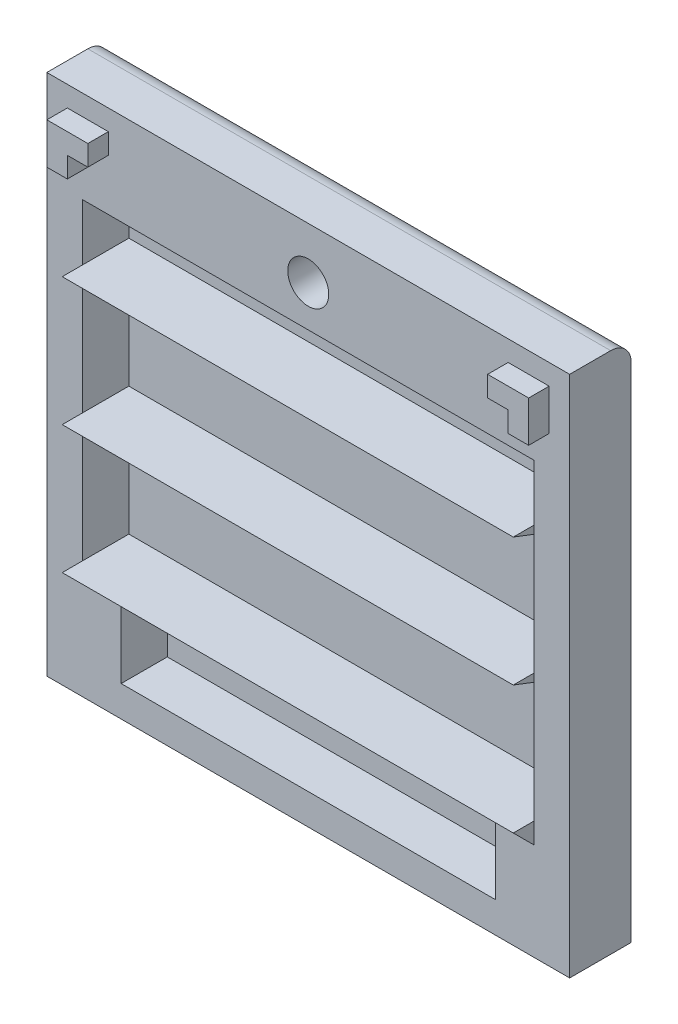
SolidWorks part; units mm, degrees
material "ABS"
ref_plane "Plano frontal" through (0, 0, 0) normal (0, 0, 1) x (1, 0, 0)
ref_plane "Plano superior" through (0, 0, 0) normal (0, 1, 0) x (1, 0, 0)
ref_plane "Plano direito" through (0, 0, 0) normal (1, 0, 0) x (0, 0, -1)
sketch "Esboço1" plane through (0, 0, 0) normal (0, 0, 1) x (1, 0, 0)
  line L1 (25.5, 25.5) -> (-25.5, 25.5)
  line L2 (25.5, 25.5) -> (25.5, -25.5)
  line L3 (25.5, -25.5) -> (-25.5, -25.5)
  line L4 (-25.5, 25.5) -> (-25.5, -25.5)
  line L5 (25.5, 25.5) -> (-25.5, -25.5) construction
  line L6 (25.5, -25.5) -> (-25.5, 25.5) construction
  point P0 (0, 0)
  dimension "D1" = 51
  dimension "D2" = 51
extrude "Ressalto-extrusão1" add sketch "Esboço1" along normal blind 6
sketch "Esboço2" plane through (0, 0, 0) normal (0, 0, -1) x (-1, 0, 0)
  line L0 (25.5, -25.5) -> (-25.5, -25.5) construction
  line L1 (-18.25, -16) -> (18.25, -16)
  line L2 (-18.25, -16) -> (-18.25, -22.5)
  line L3 (-18.25, -22.5) -> (18.25, -22.5)
  line L4 (18.25, -16) -> (18.25, -22.5)
  point P6 (0, -16)
  dimension "D1" = 36.5
  dimension "D2" = 6.5
  dimension "D3" = 3
extrude "Corte-extrusão1" cut sketch "Esboço2" against normal blind 4.5
sketch "Esboço3" plane through (0, 0, 6) normal (0, 0, 1) x (1, 0, 0)
  line L0 (25.5, 25.5) -> (-25.5, 25.5) construction
  circle A1 centre (0, 20.5) radius 2
  dimension "D1" = 4
  dimension "D2" = 5
extrude "Corte-extrusão2" cut sketch "Esboço3" against normal through all
sketch "Esboço4" plane through (0, 0, 0) normal (0, 0, -1) x (-1, 0, 0)
  line L0 (18.25, -16) -> (-18.25, -16) construction
  line L1 (-22, 16.5) -> (22, 16.5)
  line L2 (-22, 16.5) -> (-22, -14)
  line L3 (-22, -14) -> (22, -14)
  line L4 (22, 16.5) -> (22, -14)
  line L5 (-25.5, 25.5) -> (25.5, 25.5) construction
  point P4 (22, 17.2625)
  point P5 (0, 16.5)
  point P6 (-22, 16.7072)
  dimension "D1" = 9
  dimension "D2" = 2
  dimension "D3" = 44
extrude "Corte-extrusão3" cut sketch "Esboço4" against normal up to surface (4.5 mm away) up to face at (0, -19.25, 4.5)
fillet "Filete1" radius 2 1 edges at (0, 25.5, 6)
chamfer "Chanfro1" distance 1 angle 45 1 edges at (2, 20.5, 6)
sketch "Esboço5" plane through (0, 0, 0) normal (0, 0, -1) x (-1, 0, 0)
  line L0 (-25.5, -25.5) -> (-25.5, 25.5) construction
  line L1 (-23.5, 19.5) -> (-21.5, 19.5)
  line L2 (-23.5, 19.5) -> (-23.5, 23.5)
  line L3 (-23.5, 23.5) -> (-19.5, 23.5)
  line L4 (-19.5, 21.5) -> (-19.5, 23.5)
  line L5 (21.5, 19.5) -> (23.5, 19.5)
  line L6 (19.5, 21.5) -> (19.5, 23.5)
  line L7 (19.5, 23.5) -> (23.5, 23.5)
  line L8 (23.5, 19.5) -> (23.5, 23.5)
  line L11 (19.5, 21.5) -> (21.5, 21.5)
  line L12 (21.5, 19.5) -> (21.5, 21.5)
  line L15 (-19.5, 21.5) -> (-21.5, 21.5)
  line L16 (-21.5, 19.5) -> (-21.5, 21.5)
  line L17 (-25.5, 25.5) -> (25.5, 25.5) construction
  line L18 (25.5, 25.5) -> (25.5, -25.5) construction
  point P22 (-23.5, 21.5)
  point P24 (-21.5, 23.5)
  dimension "D1" = 2
  dimension "D2" = 2
  dimension "D3" = 4
  dimension "D4" = 2
  dimension "D5" = 4
extrude "Ressalto-extrusão2" add sketch "Esboço5" along normal blind 2
sketch "Esboço6" plane through (-22, 0, 0) normal (1, 0, 0) x (0, 0, -1)
  line L0 (0, -16) -> (2, -14)
  line L1 (2, -14) -> (0, -14)
  line L2 (-4.5, -1.5) -> (2, -1.5)
  line L3 (-4.5, 16.5) -> (-4.5, -14) construction
  line L4 (2, -1.5) -> (-4.5, -4)
  line L5 (0, -14) -> (0, 16.5) construction
  line L6 (-4.5, 8.5) -> (2, 11)
  line L7 (2, 11) -> (-4.5, 11)
  line L8 (-4.5, 11) -> (-4.5, 8.5)
  line L9 (-4.5, -1.5) -> (-4.5, -4)
  line L10 (0, -14) -> (0, -16)
  dimension "D1" = 2
  dimension "D2" = 2
  dimension "D3" = 2
  dimension "D4" = 12.5
  dimension "D5" = 12.5
  dimension "D6" = 2.5
extrude "Ressalto-extrusão3" add sketch "Esboço6" along normal up to surface (44 mm away) up to face at (22, 1.25, 2.25)
ref_plane "Plano1" through (0, 0, -10) normal (0, 0, 1) x (1, 0, 0)
mirror "Espelhar1" about plane through (0, 0, -10) normal (0, 0, 1) of bodies 110
delete or keep bodies "Corpo-Excluir/Manter 1" type delete bodies bodies 110
equation "\"D5@Esboço6\"=\"D4@Esboço6\""
